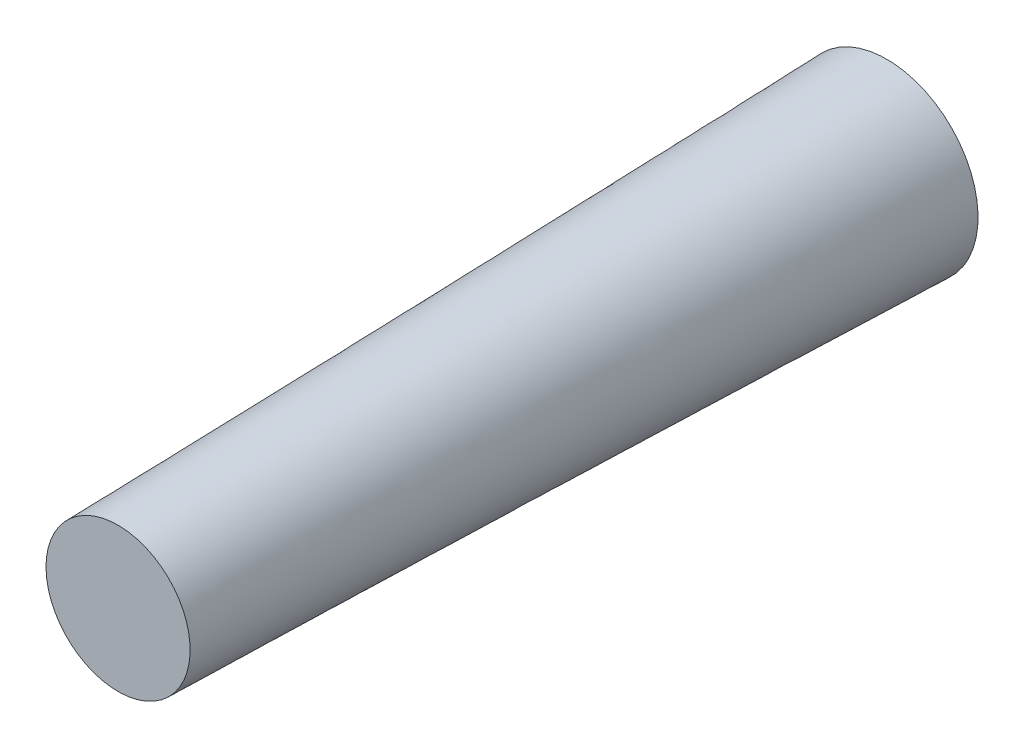
SolidWorks part; units mm, degrees
ref_plane "Front Plane" through (0, 0, 0) normal (0, 0, 1) x (1, 0, 0)
ref_plane "Top Plane" through (0, 0, 0) normal (0, 1, 0) x (1, 0, 0)
ref_plane "Right Plane" through (0, 0, 0) normal (1, 0, 0) x (0, 0, -1)
sketch "Sketch1" plane through (0, 0, 0) normal (0, 0, 1) x (1, 0, 0)
  circle A0 centre (0, 0) radius 12.065
  dimension "D1" = 24.13
ref_plane "Plane1" through (0, 0, 101.6) normal (0, 0, 1) x (1, 0, 0)
sketch "Sketch2" plane through (0, 0, 101.6) normal (0, 0, 1) x (1, 0, 0)
  circle A0 centre (0, 0) radius 9.525
  dimension "D1" = 19.05
loft "Loft1" add profiles "Sketch2", "Sketch1" connector at (-9.5249, -0.0479, 101.6) connector at (-11.6089, 3.2859, 0)
